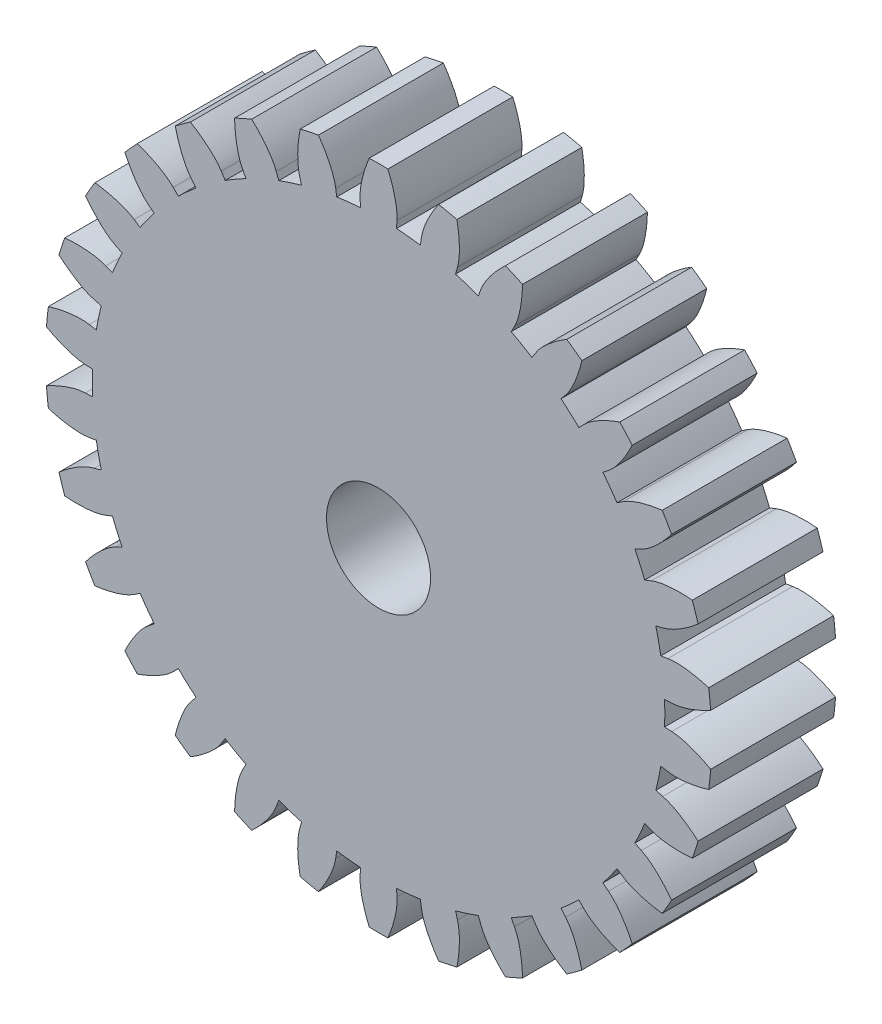
SolidWorks part; units mm, degrees
ref_plane "前视基准面" through (0, 0, 0) normal (0, 0, 1) x (1, 0, 0)
ref_plane "上视基准面" through (0, 0, 0) normal (0, 1, 0) x (1, 0, 0)
ref_plane "右视基准面" through (0, 0, 0) normal (1, 0, 0) x (0, 0, -1)
other "Configuration Table"
sketch "草图1" plane through (0, 0, 0) normal (0, 0, 1) x (1, 0, 0)
  line L0 (0, 0) -> (3, 0) construction
  line L1 (0, 0) -> (2.9959, 0.157) construction
  line L2 (0, 0) -> (2.8166, 0.1179)
  line L3 (2.9959, 0.157) -> (2.9959, -0.157) construction
  line L4 (0, 0) -> (2.8166, -0.1179)
  circle A0 centre (0, 0) radius 3.2
  circle A1 centre (0, 0) radius 3 construction
  circle A2 centre (0, 0) radius 2.75
  circle A3 centre (0, 0) radius 2.8191 construction
  circle A4 centre (0, 0) radius 0.5
  spline S0 degree 4 poles (2.8166, 0.1179) (2.8381, 0.1188) (2.8978, 0.1258) (3.0089, 0.1568) (3.1803, 0.2313) (3.3851, 0.3614) (3.6216, 0.564) (3.8603, 0.8405) (4.0761, 1.1785) (4.2561, 1.5715) (4.3861, 1.9834) (4.4688, 2.4072) (4.5085, 2.8585) (4.4993, 3.4194) (4.4024, 4.0825) (4.1788, 4.8285) (3.8049, 5.6087) (3.3237, 6.3268) (2.7489, 6.9731) (2.0986, 7.5407) (1.3811, 8.025) (0.6179, 8.4229) (-0.1939, 8.7334) (-0.914, 8.9278) (-1.5673, 9.0405) (-2.0388, 9.0934) (-2.4603, 9.1184) (-2.7399, 9.1248) (-3.1343, 9.1224) (-3.4319, 9.1032) (-3.7297, 9.081) (-3.8793, 9.0605) (-3.9757, 9.0498) knots 0 0 0 0 0 0.005604 0.015718 0.02996 0.048734 0.068727 0.096889 0.125051 0.153212 0.181374 0.209535 0.237696 0.271429 0.327752 0.384075 0.440398 0.496721 0.553044 0.609367 0.66569 0.722013 0.778336 0.834659 0.86282 0.890982 0.909091 0.931818 0.954545 0.977273 1 1 1 1 1 construction
  spline S1 degree 4 poles (2.8166, 0.1179) (2.8381, 0.1188) (2.8978, 0.1258) (3.0089, 0.1568) (3.1803, 0.2313) (3.3851, 0.3614) (3.6216, 0.564) (3.8603, 0.8405) (4.0761, 1.1785) (4.2561, 1.5715) (4.3861, 1.9834) (4.4688, 2.4072) (4.5085, 2.8585) (4.4993, 3.4194) (4.4024, 4.0825) (4.1788, 4.8285) (3.8049, 5.6087) (3.3237, 6.3268) (2.7489, 6.9731) (2.0986, 7.5407) (1.3811, 8.025) (0.6179, 8.4229) (-0.1939, 8.7334) (-0.914, 8.9278) (-1.5673, 9.0405) (-2.0388, 9.0934) (-2.3617, 9.1126) (-2.5224, 9.1187) (-2.5854, 9.1203) knots 0 0 0 0 0 0.005604 0.015718 0.02996 0.048734 0.068727 0.096889 0.125051 0.153212 0.181374 0.209535 0.237696 0.271429 0.327752 0.384075 0.440398 0.496721 0.553044 0.609367 0.66569 0.722013 0.778336 0.834659 0.86282 0.890982 0.909091 0.909091 0.909091 0.909091 0.909091
  spline S2 degree 4 poles (2.8166, -0.1179) (2.8381, -0.1188) (2.8978, -0.1258) (3.0089, -0.1568) (3.1803, -0.2313) (3.3851, -0.3614) (3.6216, -0.564) (3.8603, -0.8405) (4.0761, -1.1785) (4.2561, -1.5715) (4.3861, -1.9834) (4.4688, -2.4072) (4.5085, -2.8585) (4.4993, -3.4194) (4.4024, -4.0825) (4.1788, -4.8285) (3.8049, -5.6087) (3.3237, -6.3268) (2.7489, -6.9731) (2.0986, -7.5407) (1.3811, -8.025) (0.6179, -8.4229) (-0.1939, -8.7334) (-0.914, -8.9278) (-1.5673, -9.0405) (-2.0388, -9.0934) (-2.4603, -9.1184) (-2.7399, -9.1248) (-3.1343, -9.1224) (-3.4319, -9.1032) (-3.7297, -9.081) (-3.8793, -9.0605) (-3.9757, -9.0498) knots 0 0 0 0 0 0.005604 0.015718 0.02996 0.048734 0.068727 0.096889 0.125051 0.153212 0.181374 0.209535 0.237696 0.271429 0.327752 0.384075 0.440398 0.496721 0.553044 0.609367 0.66569 0.722013 0.778336 0.834659 0.86282 0.890982 0.909091 0.931818 0.954545 0.977273 1 1 1 1 1 construction
  spline S3 degree 4 poles (2.8166, -0.1179) (2.8381, -0.1188) (2.8978, -0.1258) (3.0089, -0.1568) (3.1803, -0.2313) (3.3851, -0.3614) (3.6216, -0.564) (3.8603, -0.8405) (4.0761, -1.1785) (4.2561, -1.5715) (4.3861, -1.9834) (4.4688, -2.4072) (4.5085, -2.8585) (4.4993, -3.4194) (4.4024, -4.0825) (4.1788, -4.8285) (3.8049, -5.6087) (3.3237, -6.3268) (2.7489, -6.9731) (2.0986, -7.5407) (1.3811, -8.025) (0.6179, -8.4229) (-0.1939, -8.7334) (-0.914, -8.9278) (-1.5673, -9.0405) (-2.0388, -9.0934) (-2.3617, -9.1126) (-2.5224, -9.1187) (-2.5854, -9.1203) knots 0 0 0 0 0 0.005604 0.015718 0.02996 0.048734 0.068727 0.096889 0.125051 0.153212 0.181374 0.209535 0.237696 0.271429 0.327752 0.384075 0.440398 0.496721 0.553044 0.609367 0.66569 0.722013 0.778336 0.834659 0.86282 0.890982 0.909091 0.909091 0.909091 0.909091 0.909091
  point P15 (2.9959, 0)
  dimension "齿顶圆直径" = 6.4
  dimension "分度圆直径" = 6
  dimension "齿根圆直径" = 5.5
  dimension "基圆直径" = 5.6382
  dimension "内孔直径" = 1
  dimension "渐近线镜像线夹角" = 3
extrude "凸台-拉伸1" add sketch "草图1" along normal blind 1.2 contours A0 | A4
extrude "切除-拉伸1" cut sketch "草图1<3>" along normal through all contours A2 S3 A0 S1 region at (3.0047, 0, 0)
sketch "草图1<3>" plane through (0, 0, 0) normal (0, 0, 1) x (1, 0, 0) same geometry as "草图1"
pattern_circular "阵列(圆周)1" count 30 every 12 about axis through (0, 0, 1.2) along (0, 0, 1) of "切除-拉伸1"
equation "\"m\"= 0.2'模数"
equation "\"z\" = 30'齿数"
equation "\"a\"= 20度'压力角"
equation "\"d\"= \"m\" * \"z\"'分度圆直径"
equation "\"da\"= ( \"z\" + 2 ) * \"m\"'齿顶圆直径"
equation "\"df\"= ( \"z\" - 2.5 ) * \"m\"'齿根圆直径"
equation "\"s\"= 0.5 * PI * \"m\"'分度圆齿厚"
equation "\"r\"= 0.38 * \"m\"'齿根圆角"
equation "\"B\"= 0.3 * \"d\"'齿厚"
equation "\"db\"= \"m\" * \"z\" * cos ( \"a\" )'基圆直径"
equation "\"rb\"= \"db\" / 2'基圆半径"
equation "\"齿顶圆直径@草图1\"= \"da\""
equation "\"分度圆直径@草图1\"= \"d\""
equation "\"齿根圆直径@草图1\"= \"df\""
equation "\"基圆直径@草图1\"= \"db\""
equation "\"渐近线镜像线夹角@草图1\"= 360 / 4 / \"z\""
equation "\"h\" = 1.2'齿轮厚度"
equation "\"ir\"= 1'内孔直径"
equation "\"内孔直径@草图1\"= \"ir\""
equation "\"齿轮厚@凸台-拉伸1\"= \"h\""
equation "\"齿轮夹角@阵列(圆周)1\"= 360 / \"z\""
equation "\"齿数@阵列(圆周)1\"= \"z\""
